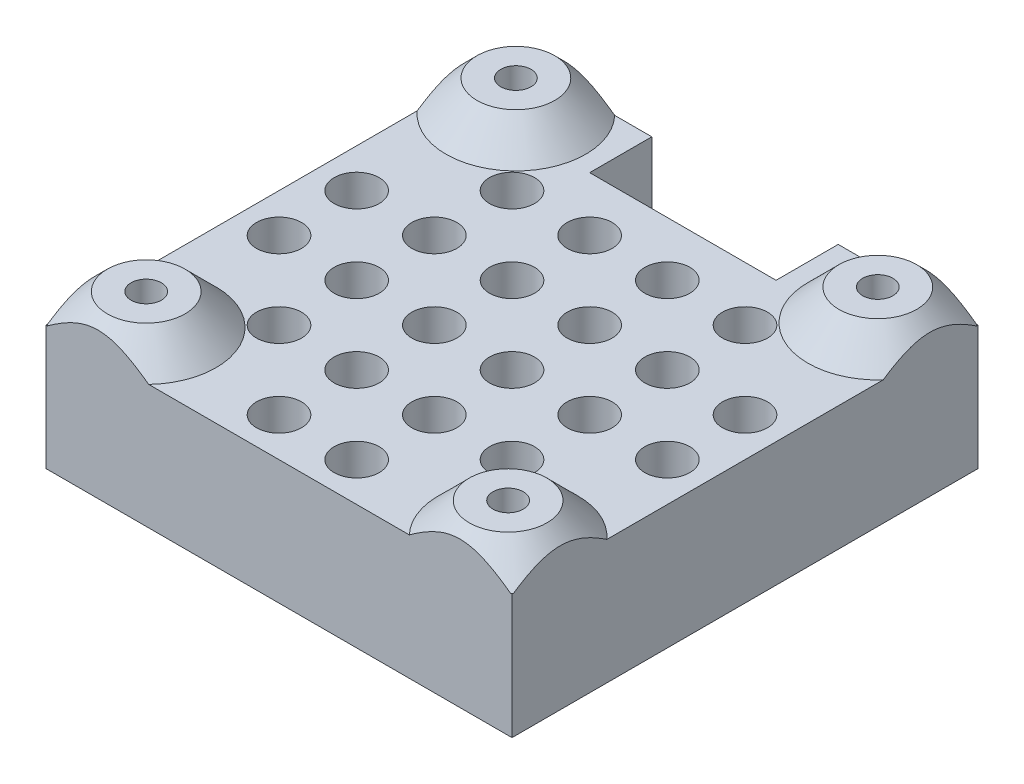
SolidWorks part; units mm, degrees
ref_plane "Front Plane" through (0, 0, 0) normal (0, 0, 1) x (1, 0, 0)
ref_plane "Top Plane" through (0, 0, 0) normal (0, 1, 0) x (1, 0, 0)
ref_plane "Right Plane" through (0, 0, 0) normal (1, 0, 0) x (0, 0, -1)
sketch "Sketch1" plane through (0, 0, 0) normal (0, 1, 0) x (1, 0, 0)
  line L1 (-15, 15) -> (15, 15)
  line L2 (-15, 15) -> (-15, -15)
  line L3 (-15, -15) -> (15, -15)
  line L4 (15, 15) -> (15, -15)
  line L5 (-15, 15) -> (15, -15) construction
  line L6 (-15, -15) -> (15, 15) construction
  point P0 (0, 0)
  dimension "D1" = 30
  dimension "D2" = 30
extrude "Boss-Extrude1" add sketch "Sketch1" along normal blind 8
sketch "Sketch5" plane through (0, 0, 0) normal (0, -1, 0) x (1, 0, 0)
  circle A0 centre (-12.5, 12.5) radius 1.45
  dimension "D1" = 2.9
  dimension "D2" = 12.5
  dimension "D3" = 12.5
extrude "Cut-Extrude3" cut sketch "Sketch5" against normal through all
pattern_linear "LPattern1" count 6 spacing 5 along (1, 0, 0) count 6 spacing 5 along (0, 0, -1) skipping (0, 1), (0, 4), (1, 0), (1, 5), (2, 5), (3, 5), (4, 0), (4, 5), (5, 1), (5, 4) of "Cut-Extrude3"
sketch "Sketch2" plane through (0, 8, 0) normal (0, 1, 0) x (1, 0, 0)
  line L1 (11.65, -11.9) -> (-11.65, -11.9) construction
  line L2 (11.65, -11.9) -> (11.65, 11.9) construction
  line L3 (11.65, 11.9) -> (-11.65, 11.9) construction
  line L4 (-11.65, -11.9) -> (-11.65, 11.9) construction
  line L5 (11.65, -11.9) -> (-11.65, 11.9) construction
  line L6 (11.65, 11.9) -> (-11.65, -11.9) construction
  circle A0 centre (-11.65, 11.9) radius 2.5
  circle A1 centre (11.65, 11.9) radius 2.5
  circle A2 centre (11.65, -11.9) radius 2.5
  circle A3 centre (-11.65, -11.9) radius 2.5
  point P2 (0, 0)
  dimension "D3" = 5
  dimension "D1" = 23.3
  dimension "D2" = 23.8
extrude "Boss-Extrude2" add sketch "Sketch2" along normal blind 2 and the other way up to surface (8 mm away) other way up to face at (-2.5, 0, 11.05)
sketch "Sketch3" plane through (0, 10, 0) normal (0, 1, 0) x (1, 0, 0)
  circle A0 centre (-11.65, 11.9) radius 0.975
  circle A1 centre (11.65, 11.9) radius 0.975
  circle A2 centre (-11.65, -11.9) radius 0.975
  circle A3 centre (11.65, -11.9) radius 0.975
  dimension "D1" = 1.95
extrude "Cut-Extrude1" cut sketch "Sketch3" against normal through all
sketch "Sketch4" plane through (0, 8, 0) normal (0, 1, 0) x (1, 0, 0)
  line L0 (15, 15) -> (-15, 15) construction
  line L1 (6, 11) -> (-6, 11)
  line L2 (6, 11) -> (6, 15)
  line L3 (6, 15) -> (-6, 15)
  line L4 (-6, 11) -> (-6, 15)
  line L5 (6, 11) -> (-6, 15) construction
  line L6 (6, 15) -> (-6, 11) construction
  point P0 (0, 13)
  dimension "D1" = 12
  dimension "D2" = 4
extrude "Cut-Extrude2" cut sketch "Sketch4" against normal through all
chamfer "Chamfer1" distance 2 angle 45 4 edges at (11.65, 8, -9.4) (11.65, 8, 14.4) (-11.65, 8, 14.4) (-11.65, 8, -9.4)
